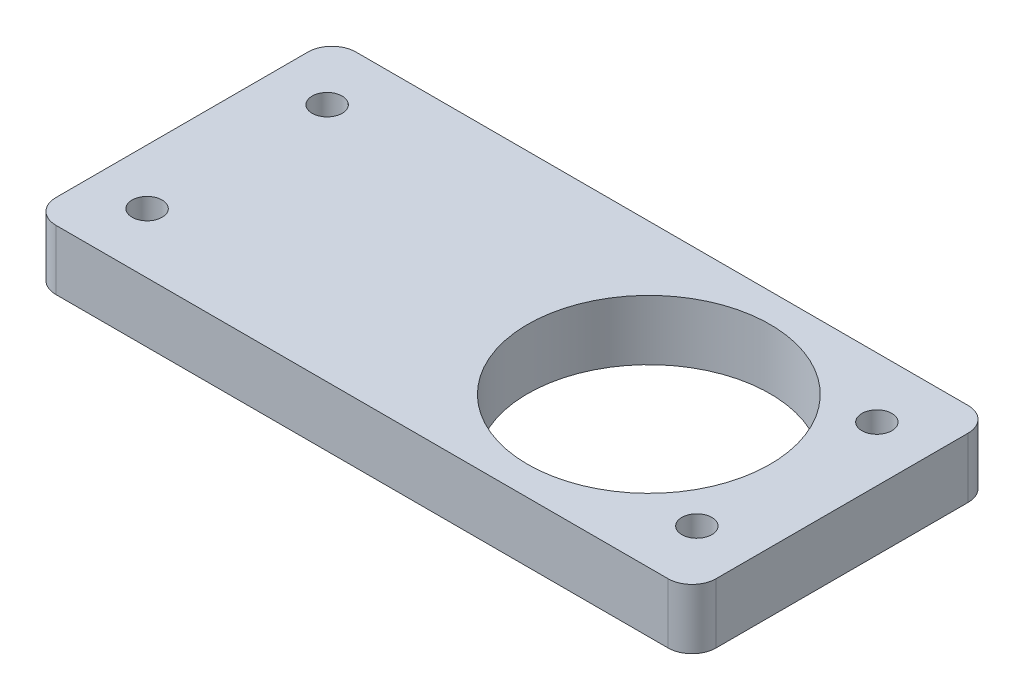
SolidWorks part; units mm, degrees
ref_plane "Front Plane" through (0, 0, 0) normal (0, 0, 1) x (1, 0, 0)
ref_plane "Top Plane" through (0, 0, 0) normal (0, 1, 0) x (1, 0, 0)
ref_plane "Right Plane" through (0, 0, 0) normal (1, 0, 0) x (0, 0, -1)
sketch "Sketch1" plane through (0, 0, 0) normal (0, 1, 0) x (1, 0, 0)
  line L0 (-2.794, 12.7) -> (60.706, 12.7) construction
  line L1 (-69.85, -31.75) -> (69.85, -31.75)
  line L2 (-69.85, -31.75) -> (-69.85, 31.75)
  line L3 (-69.85, 31.75) -> (69.85, 31.75)
  line L4 (69.85, -31.75) -> (69.85, 31.75)
  line L5 (-69.85, -31.75) -> (69.85, 31.75) construction
  line L6 (-69.85, 31.75) -> (69.85, -31.75) construction
  line L7 (60.706, 12.7) -> (60.706, -12.7) construction
  line L8 (60.706, -12.7) -> (-2.794, -12.7) construction
  line L9 (-2.794, -12.7) -> (-2.794, 12.7) construction
  line L10 (-2.794, 12.7) -> (60.706, -12.7) construction
  line L11 (60.706, 12.7) -> (-2.794, -12.7) construction
  line L12 (-58.166, -19.05) -> (-58.166, 19.05) construction
  line L13 (-58.166, 19.05) -> (58.166, 19.05) construction
  line L14 (58.166, 19.05) -> (58.166, -19.05) construction
  line L15 (58.166, -19.05) -> (-58.166, -19.05) construction
  circle A5 centre (28.956, 0) radius 25.654
  circle A6 centre (-58.166, -19.05) radius 3.175
  circle A7 centre (-58.166, 19.05) radius 3.175
  circle A8 centre (58.166, 19.05) radius 3.175
  circle A9 centre (58.166, -19.05) radius 3.175
  point P0 (0, 0)
  point P7 (0, 0)
  point P18 (28.956, 0)
  point P23 (0, -31.75)
  point P24 (0, -19.05)
  point P25 (58.166, 0)
  dimension "D1" = 28.956
  dimension "D6" = 6.35
  dimension "D7" = 51.308
  dimension "D2" = 63.5
  dimension "D3" = 25.4
  dimension "D4" = 63.5
  dimension "D5" = 139.7
  dimension "D8" = 38.1
  dimension "D9" = 116.332
extrude "Boss-Extrude1" add sketch "Sketch1" along normal blind 12.7
fillet "Fillet1" radius 5.08 4 edges at (-69.85, 6.35, -31.75) (69.85, 6.35, -31.75) (69.85, 6.35, 31.75) (-69.85, 6.35, 31.75)
